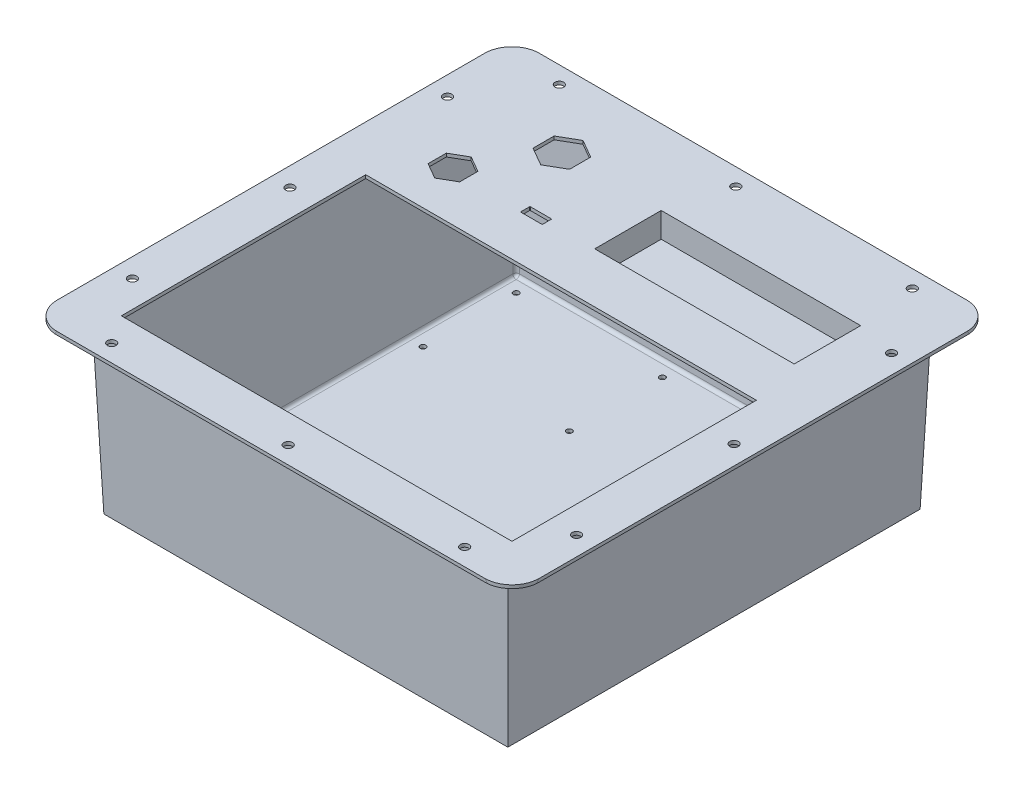
SolidWorks part; units mm, degrees
ref_plane "Front Plane" through (0, 0, 0) normal (0, 0, 1) x (1, 0, 0)
ref_plane "Top Plane" through (0, 0, 0) normal (0, 1, 0) x (1, 0, 0)
ref_plane "Right Plane" through (0, 0, 0) normal (1, 0, 0) x (0, 0, -1)
sketch "Sketch2" plane through (0, 0, 0) normal (0, 1, 0) x (1, 0, 0)
  line L5 (27.5, 174.5) -> (262.5, 174.5)
  line L6 (27.5, 174.5) -> (27.5, 27.5)
  line L7 (27.5, 27.5) -> (262.5, 27.5)
  line L8 (262.5, 174.5) -> (262.5, 27.5)
  line L16 (93.76, 207.05) -> (93.76, 201.95)
  line L20 (93.76, 201.95) -> (106.24, 201.95)
  line L21 (106.24, 201.95) -> (106.24, 207.05)
  line L22 (106.24, 207.05) -> (93.76, 207.05)
  line L27 (106.23, 207.35) -> (93.77, 207.35)
  line L28 (93.46, 207.04) -> (93.46, 201.96)
  line L29 (93.77, 201.65) -> (106.23, 201.65)
  line L30 (106.54, 201.96) -> (106.54, 207.04)
  line L31 (93.46, 201.65) -> (106.54, 201.65) construction
  line L32 (106.54, 201.65) -> (106.54, 207.35) construction
  line L33 (93.46, 207.35) -> (93.46, 201.65) construction
  line L34 (106.54, 207.35) -> (93.46, 207.35) construction
  line L35 (135, 248.48) -> (255, 248.48)
  line L36 (16.51, 0) -> (273.49, 0)
  line L37 (0, 16.51) -> (0, 273.49)
  line L38 (16.51, 290) -> (273.49, 290)
  line L39 (290, 16.51) -> (290, 273.49)
  line L40 (50, 193.5303) -> (59.5, 199.0152)
  line L41 (59.5, 199.0152) -> (59.5, 209.9848)
  line L42 (59.5, 209.9848) -> (50, 215.4697)
  line L43 (50, 215.4697) -> (40.5, 209.9848)
  line L44 (40.5, 209.9848) -> (40.5, 199.0152)
  line L45 (40.5, 199.0152) -> (50, 193.5303)
  line L46 (75, 232.2983) -> (86, 238.6491)
  line L47 (86, 238.6491) -> (86, 251.3509)
  line L48 (86, 251.3509) -> (75, 257.7017)
  line L49 (75, 257.7017) -> (64, 251.3509)
  line L50 (64, 251.3509) -> (64, 238.6491)
  line L51 (64, 238.6491) -> (75, 232.2983)
  line L52 (135, 248.48) -> (135, 198.48)
  line L53 (135, 198.48) -> (255, 198.48)
  line L54 (255, 248.48) -> (255, 198.48)
  line L59 (75, 245) -> (75, 201.96) construction
  arc A16 (106.23, 201.65) -> (106.54, 201.96) centre (106.23, 201.96) ccw
  arc A17 (93.46, 201.96) -> (93.77, 201.65) centre (93.77, 201.96) ccw
  arc A18 (106.23, 207.35) -> (106.54, 207.04) centre (106.23, 207.04) cw
  arc A19 (93.77, 207.35) -> (93.46, 207.04) centre (93.77, 207.04) ccw
  arc A20 (273.49, 0) -> (290, 16.51) centre (273.49, 16.51) ccw
  arc A21 (16.51, 0) -> (0, 16.51) centre (16.51, 16.51) cw
  arc A22 (273.49, 290) -> (290, 273.49) centre (273.49, 273.49) cw
  arc A23 (0, 273.49) -> (16.51, 290) centre (16.51, 273.49) cw
  circle A24 centre (50, 204.5) radius 9.5 construction
  circle A25 centre (75, 245) radius 11 construction
  point P9 (0, 0)
  point P12 (290, 290)
  point P15 (0, 290)
  point P29 (93.76, 204.5)
  point P30 (100, 201.95)
  point P43 (75, 223.48)
  point P47 (135, 223.48)
  dimension "D3" = 290
  dimension "D8" = 27.5
  dimension "D15" = 0.31
  dimension "D6" = 16.51
  dimension "D14" = 19
  dimension "D18" = 22
  dimension "D2" = 290
  dimension "D4" = 235
  dimension "D5" = 147
  dimension "D7" = 0.3
  dimension "D9" = 27.5
  dimension "D10" = 30
  dimension "D11" = 50
  dimension "D12" = 5.1
  dimension "D13" = 12.48
  dimension "D16" = 50
  dimension "D17" = 25
  dimension "D19" = 45
  dimension "D20" = 120
  dimension "D21" = 50
  dimension "D22" = 43.04
  dimension "D23" = 35
extrude "Boss-Extrude1" add sketch "Sketch2" along normal blind 2 contours A23 L37 A21 L36 A20 L39 A22 L38 A19 L27 A18 L30 A16 L29 A17 L28 L45 L44 L43 L42 L41 L40 L5 L8 L7 L6 | L35 L54 L53 L52 region at (7.7357, 0, -7.7357)
sketch "Sketch6" plane through (0, 0, 0) normal (0, 0, 1) x (1, 0, 0)
  line L0 (20, 0) -> (20, -100)
  line L1 (16.51, 0) -> (273.49, 0) construction
  line L2 (20, -100) -> (270, -100)
  line L3 (270, -100) -> (270, 0)
  line L4 (290, 2) -> (290, 0) construction
  line L5 (20, 0) -> (270, 0)
  dimension "D1" = 20
  dimension "D2" = 20
  dimension "D3" = 100
extrude "Boss-Extrude2" add sketch "Sketch6" against normal blind 255 from offset 17.5 offset against normal yes
sketch "Sketch7" plane through (0, 0, 0) normal (0, 0, 1) x (1, 0, 0)
  line L0 (0, 2) -> (0.0698, 0)
  line L1 (0, 0) -> (16.51, 0) construction
  line L2 (145, 16.7397) -> (145, -40.9382) construction
  line L3 (0, 2) -> (0, 0) construction
  line L4 (0, 2) -> (0, 0)
  line L5 (0, 0) -> (0.0698, 0)
  line L6 (290, 0) -> (289.9302, 0)
  line L7 (290, 2) -> (290, 0)
  line L8 (290, 2) -> (289.9302, 0)
  line L9 (16.51, 2) -> (273.49, 2) construction
  line L10 (20, 0) -> (23.4921, -100)
  line L11 (20, -100) -> (270, -100) construction
  line L12 (20, 0) -> (20, -100) construction
  line L13 (20, 0) -> (20, -100)
  line L14 (20, -100) -> (23.4921, -100)
  line L15 (270, 0) -> (266.5079, -100)
  line L16 (270, 0) -> (270, -100)
  line L17 (270, -100) -> (266.5079, -100)
  point P16 (145, 2)
  dimension "D1" = 2
  dimension "D2" = 2
extrude "Cut-Extrude1" cut sketch "Sketch7" against normal through all both and the other way through all
sketch "Sketch8" plane through (0, 0, 0) normal (1, 0, 0) x (0, 0, -1)
  line L0 (0, 2) -> (0.0698, 0)
  line L1 (0, 0) -> (14.993, 0) construction
  line L2 (17.5, 0) -> (20.9921, -100)
  line L3 (272.5, -100) -> (17.5, -100) construction
  line L4 (17.5, 0) -> (17.5, -100) construction
  line L5 (0, 2) -> (0, 0) construction
  line L6 (0, 2) -> (0, 0)
  line L7 (17.5, 0) -> (17.5, -100)
  line L8 (17.5, -100) -> (20.9921, -100)
  line L9 (145, 2) -> (145, -50.2371) construction
  line L10 (16.51, 2) -> (273.49, 2) construction
  line L11 (0, 0) -> (0.0698, 0)
  line L12 (290, 0) -> (289.9302, 0)
  line L13 (272.5, -100) -> (269.0079, -100)
  line L14 (272.5, 0) -> (272.5, -100)
  line L15 (290, 2) -> (290, 0)
  line L16 (272.5, 0) -> (269.0079, -100)
  line L17 (290, 2) -> (289.9302, 0)
  dimension "D1" = 2
  dimension "D2" = 2
extrude "Cut-Extrude2" cut sketch "Sketch8" against normal through all both and the other way through all
sketch "Sketch10" plane through (0, 2, 0) normal (0, 1, 0) x (1, 0, 0)
  line L0 (16.51, 290) -> (273.49, 290) construction
  line L1 (0, 16.51) -> (0, 273.49) construction
  line L2 (0, 145) -> (290, 145) construction
  line L3 (290, 16.51) -> (290, 273.49) construction
  line L4 (145, 290) -> (145, 0) construction
  line L5 (16.51, 0) -> (273.49, 0) construction
  circle A1 centre (11.428, 50.258) radius 2.6
  circle A2 centre (38.828, 10.358) radius 2.6
  circle A3 centre (11.428, 145) radius 2.6
  circle A4 centre (145, 10.358) radius 2.6
  circle A5 centre (145, 279.642) radius 2.6
  circle A6 centre (38.828, 279.642) radius 2.6
  circle A7 centre (11.428, 239.742) radius 2.6
  circle A8 centre (251.172, 10.358) radius 2.6
  circle A9 centre (278.572, 50.258) radius 2.6
  circle A10 centre (278.572, 145) radius 2.6
  circle A11 centre (278.572, 239.742) radius 2.6
  circle A12 centre (251.172, 279.642) radius 2.6
  point P12 (0, 145)
  dimension "D1" = 5.2
  dimension "D2" = 27.4
  dimension "D4" = 106.172
  dimension "D3" = 39.9
  dimension "D5" = 94.742
extrude "Cut-Extrude4" cut sketch "Sketch10" against normal blind 2.54
sketch "Sketch11" plane through (0, 2, 0) normal (0, 1, 0) x (1, 0, 0)
  line L1 (135, 204.75) -> (255, 204.75)
  line L2 (135, 204.75) -> (135, 244.75)
  line L3 (135, 244.75) -> (255, 244.75)
  line L4 (255, 204.75) -> (255, 244.75)
  line L5 (75.1658, 245) -> (75.1658, 204.5) construction
  line L7 (93.46, 207.04) -> (93.46, 201.96) construction
  line L8 (86, 238.6491) -> (86, 251.3509) construction
  line L9 (290, 16.51) -> (290, 273.49) construction
  point P8 (93.46, 204.5)
  point P12 (86, 245)
  point P13 (75.1658, 224.75)
  point P14 (135, 224.75)
  dimension "D1" = 120
  dimension "D2" = 40
  dimension "D3" = 40.5
  dimension "D4" = 35
extrude "Cut-Extrude5" cut sketch "Sketch11" against normal blind 15
shell "Shell1" thickness 2 removed face at (145, 1.2499, -0.0262) removed face at (145, 1.2499, -289.9738) removed face at (289.9738, 1.2499, -145) removed face at (0.0262, 1.2499, -145) removed face at (145, 0, -101) removed face at (100, 0, -204.5) removed face at (50, 0, -204.5) removed face at (75, 0, -245)
fillet "Fillet1" radius 2 24 edges at (195, 0, -202.75) (195, 0, -246.75) (257, -7.5, -246.75) (257, -7.5, -202.75) (257, 0, -224.75) (195, -15, -202.75) (257, -15, -224.75) (195, -15, -246.75) (133, -7.5, -202.75) (133, -15, -224.75) (133, -7.5, -246.75) (133, 0, -224.75) (22.0012, 0, -145) (145, 0, -19.5012) (267.9988, 0, -145) (145, 0, -270.4988) (266.2877, -49, -268.7877) (266.2877, -49, -21.2123) (23.7123, -49, -268.7877) (23.7123, -49, -21.2123) (264.5765, -98, -145) (145, -98, -22.9235) (25.4235, -98, -145) (145, -98, -267.0765)
sketch "Sketch12" plane through (0, -98, 0) normal (0, 1, 0) x (1, 0, 0)
  line L0 (34.3548, 195.1452) -> (122.3548, 195.1452) construction
  line L1 (27.3548, 202.1452) -> (27.3548, 258.1452) construction
  line L2 (34.3548, 265.1452) -> (122.3548, 265.1452) construction
  line L3 (129.3548, 202.1452) -> (129.3548, 258.1452) construction
  line L4 (27.3548, 195.1452) -> (129.3548, 265.1452) construction
  line L5 (27.3548, 265.1452) -> (129.3548, 195.1452) construction
  line L6 (262.6452, 265.1452) -> (27.3548, 265.1452) construction
  line L7 (27.3548, 265.1452) -> (27.3548, 24.8548) construction
  arc A0 (122.3548, 265.1452) -> (129.3548, 258.1452) centre (122.3548, 258.1452) cw construction
  arc A1 (122.3548, 195.1452) -> (129.3548, 202.1452) centre (122.3548, 202.1452) ccw construction
  arc A2 (34.3548, 195.1452) -> (27.3548, 202.1452) centre (34.3548, 202.1452) cw construction
  arc A3 (27.3548, 258.1452) -> (34.3548, 265.1452) centre (34.3548, 258.1452) cw construction
  circle A4 centre (34.3548, 258.1452) radius 4 construction
  circle A5 centre (122.3548, 258.1452) radius 4 construction
  circle A6 centre (34.3548, 202.1452) radius 4 construction
  circle A7 centre (122.3548, 202.1452) radius 4 construction
  point P0 (78.3548, 230.1452)
  point P7 (122.3548, 258.1452)
  point P10 (122.3548, 202.1452)
  point P13 (34.3548, 202.1452)
  point P16 (34.3548, 258.1452)
  point P28 (34.3548, 258.1452)
  point P31 (122.3548, 258.1452)
  point P34 (122.3548, 202.1452)
  point P37 (34.3548, 202.1452)
  point P47 (34.3548, 258.1452)
  point P49 (122.3548, 258.1452)
  point P51 (122.3548, 202.1452)
  point P53 (34.3548, 202.1452)
  point P56 (0, 0)
  dimension "D3" = 7
  dimension "D4" = 8
  dimension "D1" = 102
  dimension "D2" = 70
sketch "Sketch18" plane through (0, -98, 0) normal (0, 1, 0) x (1, 0, 0)
  point P0 (34.3548, 258.1452)
  point P3 (122.3548, 258.1452)
  point P6 (122.3548, 202.1452)
  point P9 (34.3548, 202.1452)
hole_wizard "M3 Clearance Hole1" positions "Sketch18" profile "Sketch17" hole size "M3" standard "ISO" end condition through all
sketch "Sketch17" plane through (34.3548, -98, -258.1452) normal (1, 0, 0) x (0, 0, 1)
  line L0 (0, 0) -> (0, 2)
  line L1 (0, 2) -> (1.7, 2)
  line L2 (1.7, 2) -> (1.7, 0)
  line L5 (1.7, 0) -> (0, 0)
  line L11 (0, -6.35) -> (0, 107.95) construction
  dimension "Thru Hole Dia." = 3.4
  dimension "Thru Hole Depth" = 2
